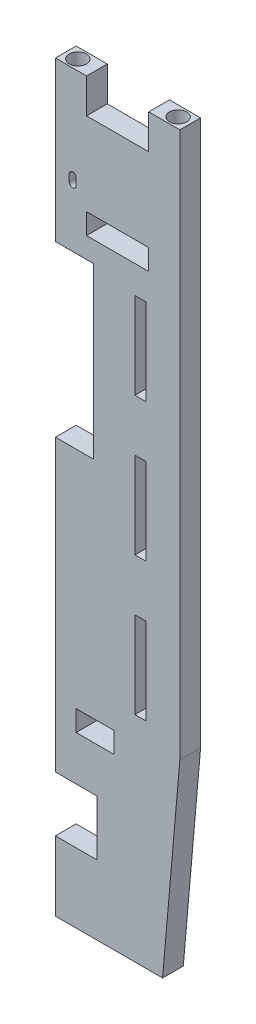
SolidWorks part; units mm, degrees
material "Plywood"
ref_plane "Plan de face" through (0, 0, 0) normal (0, 0, 1) x (1, 0, 0)
ref_plane "Plan de dessus" through (0, 0, 0) normal (0, 1, 0) x (1, 0, 0)
ref_plane "Plan de droite" through (0, 0, 0) normal (1, 0, 0) x (0, 0, -1)
sketch "Esquisse1" plane through (0, 0, 0) normal (0, 0, 1) x (1, 0, 0)
  line L1 (0, 0) -> (36, 0)
  line L2 (0, 0) -> (0, 215)
  line L3 (0, 215) -> (36, 215)
  line L4 (36, 0) -> (36, 215)
  dimension "D1" = 36
  dimension "D2" = 215
extrude "Boss.-Extru.1" add sketch "Esquisse1" along normal blind 6
sketch "Esquisse2" plane through (0, 215, 0) normal (0, 1, 0) x (1, 0, 0)
  line L0 (36, 0) -> (0, 0) construction
  line L1 (9, 0) -> (27, 0)
  line L2 (9, 0) -> (9, -6)
  line L3 (9, -6) -> (27, -6)
  line L4 (27, 0) -> (27, -6)
  line L5 (36, -6) -> (0, -6) construction
  line L6 (0, -6) -> (0, 0) construction
  dimension "D1" = 9
  dimension "D2" = 18
extrude "Enlèv. mat.-Extru.1" cut sketch "Esquisse2" against normal blind 10
sketch "Esquisse3" plane through (0, 0, 6) normal (0, 0, 1) x (1, 0, 0)
  line L0 (36, 215) -> (27, 215) construction
  line L1 (27, 175) -> (9, 175)
  line L2 (27, 175) -> (27, 181)
  line L3 (27, 181) -> (9, 181)
  line L4 (9, 175) -> (9, 181)
  line L5 (0, 215) -> (0, 0) construction
  dimension "D1" = 34
  dimension "D2" = 6
  dimension "D3" = 9
  dimension "D4" = 18
extrude "Enlèv. mat.-Extru.2" cut sketch "Esquisse3" against normal through all
sketch "Esquisse4" plane through (0, 0, 0) normal (0, 0, -1) x (-1, 0, 0)
  line L0 (0, 215) -> (0, 0) construction
  line L1 (0, 169) -> (-11, 169)
  line L2 (0, 169) -> (0, 120)
  line L3 (0, 120) -> (-11, 120)
  line L4 (-11, 169) -> (-11, 120)
  dimension "D1" = 0
  dimension "D2" = 0
  dimension "D3" = 11
extrude "Enlèv. mat.-Extru.3" cut sketch "Esquisse4" against normal through all
sketch "Esquisse5" plane through (0, 215, 0) normal (0, 1, 0) x (1, 0, 0)
  line L0 (0, -6) -> (0, 0) construction
  line L3 (9, 0) -> (0, 0) construction
  circle A0 centre (3.5, -3) radius 2.5
  dimension "D1" = 5
  dimension "D2" = 3.5
  dimension "D3" = 3
extrude "Enlèv. mat.-Extru.4" cut sketch "Esquisse5" against normal blind 10
pattern_linear "Répétition linéaire1" count 2 spacing 29 along (1, 0, 0) of "Enlèv. mat.-Extru.4"
sketch "Esquisse6" plane through (0, 0, 0) normal (0, 0, -1) x (-1, 0, 0)
  line L0 (-5.0011, 185.9733) -> (-5.0011, 187.9733) construction
  line L1 (-6.0011, 185.9733) -> (-6.0011, 187.9733)
  line L2 (-4.0011, 185.9733) -> (-4.0011, 187.9733)
  arc A0 (-6.0011, 185.9733) -> (-4.0011, 185.9733) centre (-5.0011, 185.9733) ccw
  arc A1 (-4.0011, 187.9733) -> (-6.0011, 187.9733) centre (-5.0011, 187.9733) ccw
  point P2 (-5.0011, 186.9733)
  point P7 (-5.0011, 186.9733)
  dimension "D1" = 1
  dimension "D2" = 2
extrude "Enlèv. mat.-Extru.5" cut sketch "Esquisse6" against normal blind 10
sketch "Esquisse8" plane through (0, 0, 0) normal (0, 0, -1) x (-1, 0, 0)
  line L0 (0, 120) -> (0, 0) construction
  line L1 (-6, 49) -> (-17, 49)
  line L2 (-6, 49) -> (-6, 55)
  line L3 (-6, 55) -> (-17, 55)
  line L4 (-17, 49) -> (-17, 55)
  line L5 (0, 20.1122) -> (-12, 20.1122)
  line L6 (0, 20.1122) -> (0, 36.1122)
  line L7 (0, 36.1122) -> (-12, 36.1122)
  line L8 (-12, 20.1122) -> (-12, 36.1122)
  dimension "D1" = 12
  dimension "D2" = 16
extrude "Enlèv. mat.-Extru.6" cut sketch "Esquisse8" against normal through all
sketch "Esquisse9" plane through (0, 0, 0) normal (0, 0, 1) x (1, 0, 0)
  line L1 (26.2, 62) -> (23, 62)
  line L2 (26.2, 62) -> (26.2, 87)
  line L3 (26.2, 87) -> (23, 87)
  line L4 (23, 62) -> (23, 87)
  line L5 (23, 167) -> (26, 167) construction
  line L6 (23, 102) -> (26.2, 102)
  line L7 (23, 102) -> (23, 127)
  line L8 (23, 127) -> (26.2, 127)
  line L9 (26.2, 102) -> (26.2, 127)
  line L10 (26.2, 142) -> (23, 142)
  line L11 (26.2, 142) -> (26.2, 167)
  line L12 (26.2, 167) -> (23, 167)
  line L13 (23, 142) -> (23, 167)
  line L15 (23, 149) -> (23, 167) construction
  dimension "D1" = 3.2
  dimension "D2" = 0
  dimension "D3" = 25
  dimension "D4" = 25
  dimension "D5" = 25
  dimension "D6" = 15
  dimension "D7" = 15
  dimension "D8" = 0
extrude "Enlèv. mat.-Extru.8" cut sketch "Esquisse9" along normal through all
chamfer "Chanfrein1" distance 5 angle 85 1 edges at (36, 0, 3) first distance on face at (18, 0, 3)
